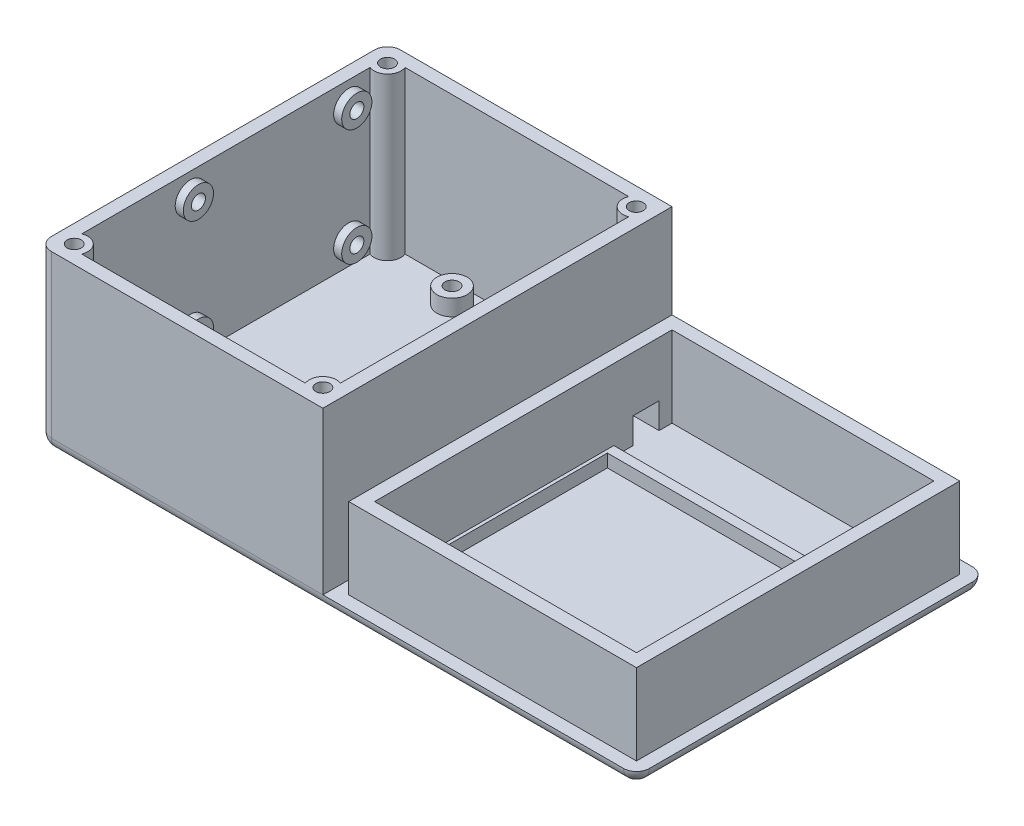
SolidWorks part; units mm, degrees
ref_plane "Front Plane" through (0, 0, 0) normal (0, 0, 1) x (1, 0, 0)
ref_plane "Top Plane" through (0, 0, 0) normal (0, 1, 0) x (1, 0, 0)
ref_plane "Right Plane" through (0, 0, 0) normal (1, 0, 0) x (0, 0, -1)
sketch "Sketch1" plane through (0, 0, 0) normal (0, 1, 0) x (1, 0, 0)
  line L1 (-88.5, -54) -> (88.5, -54)
  line L2 (-92.5, -50) -> (-92.5, 50)
  line L3 (-88.5, 54) -> (88.5, 54)
  line L4 (92.5, -50) -> (92.5, 50)
  line L5 (-92.5, -54) -> (92.5, 54) construction
  line L6 (-92.5, 54) -> (92.5, -54) construction
  arc A0 (-88.5, -54) -> (-92.5, -50) centre (-88.5, -50) cw
  arc A1 (88.5, -54) -> (92.5, -50) centre (88.5, -50) ccw
  arc A2 (88.5, 54) -> (92.5, 50) centre (88.5, 50) cw
  arc A3 (-92.5, 50) -> (-88.5, 54) centre (-88.5, 50) cw
  point P0 (0, 0)
  dimension "D1" = 4
  dimension "D2" = 185
  dimension "D3" = 100
extrude "Boss-Extrude1" add sketch "Sketch1" along normal blind 4
fillet "Fillet1" radius 4 8 edges at (0, 0, 54) (91.3284, 0, 52.8284) (92.5, 0, 0) (91.3284, 0, -52.8284) (0, 0, -54) (-91.3284, 0, -52.8284) (-92.5, 0, 0) (-91.3284, 0, 52.8284)
sketch "Sketch4" plane through (0, 4, 0) normal (0, 1, 0) x (1, 0, 0)
  line L0 (-88.5, -54) -> (88.5, -54) construction
  line L1 (92.5, -50) -> (92.5, 50) construction
  line L2 (88.5, 54) -> (-88.5, 54) construction
  line L3 (-92.5, 50) -> (-92.5, -50) construction
  line L4 (-88.5, -54) -> (88.5, -54)
  line L5 (92.5, -50) -> (92.5, 50)
  line L6 (88.5, 54) -> (-88.5, 54)
  line L7 (-92.5, 50) -> (-92.5, -50)
  line L8 (-88.5, -50) -> (88.5, -50)
  line L9 (88.5, -50) -> (88.5, 50)
  line L10 (88.5, 50) -> (-88.5, 50)
  line L11 (-88.5, 50) -> (-88.5, -50)
  line L12 (3.5, 46) -> (84.5, 46)
  line L13 (3.5, 54) -> (-0.5, 54)
  line L14 (3.5, 54) -> (3.5, -54)
  line L15 (3.5, -54) -> (-0.5, -54)
  line L16 (-0.5, 54) -> (-0.5, -54)
  line L17 (-4.5, 54) -> (-8.5, 54)
  line L18 (-4.5, 54) -> (-4.5, -54)
  line L19 (-4.5, -54) -> (-8.5, -54)
  line L20 (-8.5, 54) -> (-8.5, -54)
  line L21 (84.5, 46) -> (84.5, -46)
  line L22 (84.5, -46) -> (3.5, -46)
  arc A0 (-88.5, 54) -> (-92.5, 50) centre (-88.5, 50) ccw construction
  arc A1 (-92.5, -50) -> (-88.5, -54) centre (-88.5, -50) ccw construction
  arc A2 (88.5, -54) -> (92.5, -50) centre (88.5, -50) ccw construction
  arc A3 (92.5, 50) -> (88.5, 54) centre (88.5, 50) ccw construction
  arc A4 (-92.5, -50) -> (-88.5, -54) centre (-88.5, -50) ccw
  arc A5 (88.5, -54) -> (92.5, -50) centre (88.5, -50) ccw
  arc A6 (92.5, 50) -> (88.5, 54) centre (88.5, 50) ccw
  arc A7 (-88.5, 54) -> (-92.5, 50) centre (-88.5, 50) ccw
  arc A8 (88.5, -50) -> (88.5, -50) centre (88.5, -50) ccw
  arc A9 (88.5, 50) -> (88.5, 50) centre (88.5, 50) ccw
  arc A10 (-88.5, 50) -> (-88.5, 50) centre (-88.5, 50) ccw
  arc A11 (-88.5, -50) -> (-88.5, -50) centre (-88.5, -50) ccw
  arc M17 (-92.5, -50) -> (-88.5, -54) centre (-88.5, -50) ccw
  line M18 (-88.5, -54) -> (88.5, -54)
  line M22 (88.5, 54) -> (-88.5, 54)
  arc M23 (-88.5, 54) -> (-92.5, 50) centre (-88.5, 50) ccw
  line M24 (-92.5, 50) -> (-92.5, -50)
  dimension "D2" = 4
  dimension "D3" = 4
  dimension "D4" = 4
  dimension "D5" = 85
  dimension "D6" = 4
  dimension "D7" = 4
  dimension "D8" = 4
  dimension "D1" = 4
extrude "Boss-Extrude2" add sketch "Sketch4" along normal blind 50 contours L20 L8 L11 L10 M22 M23 M24 M17 M18 | L6 L20 L10 L18 | L10 L20 L8 L18 | L8 L20 L4 L18 region at (-90.361, 4, 51.861) region at (-6.5, 4, 52) region at (-6.5, 4, 0) region at (-6.5, 4, -52)
extrude "Boss-Extrude3" add sketch "Sketch4<3>" along normal blind 25 contours L10 L16 L8 L14 | L21 L22 L14 L8 L9 L10 L12 region at (1.5, 4, 0) region at (4.8124, 4, 48)
sketch "Sketch4<3>" plane through (0, 4, 0) normal (0, 1, 0) x (1, 0, 0) same geometry as "Sketch4"
sketch "Sketch5" plane through (-8.5, 0, 0) normal (-1, 0, 0) x (0, 0, 1)
  line L0 (-50, 4) -> (50, 4) construction
  line L1 (-42, 4) -> (-34, 4)
  line L2 (-42, 4) -> (-42, 12)
  line L3 (-42, 12) -> (-34, 12)
  line L4 (-34, 4) -> (-34, 12)
  line L6 (-46, 4) -> (-30, 4)
  line L7 (-46, 4) -> (-46, 16)
  line L8 (-46, 16) -> (-30, 16)
  line L9 (-30, 4) -> (-30, 16)
  line L10 (-50, 54) -> (-50, 4) construction
  point P6 (-38, 12)
  point P12 (-38, 16)
  line M5 (-50, 4) -> (50, 4)
  dimension "D1" = 8
  dimension "D2" = 4
  dimension "D3" = 4
  dimension "D4" = 4
extrude "Boss-Extrude4" add sketch "Sketch5" against normal up to surface (12 mm away) contours L9 L8 L7 L2 L3 L4 M5 region at (-8.5, 4.2, -44) up to face at (3.5, 16.5, 0)
extrude "Cut-Extrude1" cut sketch "Sketch5<3>" against normal up to surface (12 mm away) contours L4 L3 L2 M5 region at (-8.5, 8, -38) up to face at (3.5, 16.5, 0)
sketch "Sketch5<3>" plane through (-8.5, 0, 0) normal (-1, 0, 0) x (0, 0, 1) same geometry as "Sketch5"
sketch "Sketch6" plane through (0, 4, 0) normal (0, 1, 0) x (1, 0, 0)
  line L0 (5, 24.5) -> (83, 24.5) construction
  line L1 (4.5, 25) -> (83.5, 25)
  line L2 (4.5, 25) -> (4.5, -25)
  line L3 (4.5, -25) -> (83.5, -25)
  line L4 (83.5, 25) -> (83.5, -25)
  line L5 (5, -24.5) -> (5, 24.5) construction
  line L6 (88.5, -50) -> (88.5, 50) construction
  line L7 (88.5, 28) -> (3.5, 28)
  line L8 (88.5, 28) -> (88.5, -28)
  line L9 (88.5, -28) -> (3.5, -28)
  line L10 (3.5, 28) -> (3.5, -28)
  line L11 (3.5, 34) -> (3.5, -46) construction
  point P8 (5, 0)
  point P9 (4.5, 0)
  point P10 (44, 24.5)
  point P11 (44, 25)
  point P20 (3.5, 0)
  line M15 (3.5, 34) -> (3.5, -46)
  dimension "D1" = 0.5
  dimension "D2" = 0.5
  dimension "D3" = 3
extrude "Cut-Extrude2" cut sketch "Sketch6" against normal blind 1 contours L4 L1 L2 L3 region at (44, 4, 0)
extrude "Boss-Extrude5" add sketch "Sketch6<3>" along normal blind 3 contours L9 L7 L1 L4 L3 L2 M15 region at (87.4821, 4, 0)
sketch "Sketch6<3>" plane through (0, 4, 0) normal (0, 1, 0) x (1, 0, 0) same geometry as "Sketch6"
sketch "Sketch7" plane through (0, 4, 0) normal (0, 1, 0) x (1, 0, 0)
  line L2 (-88.5, 50) -> (-86.962, 48.462) construction
  line L3 (-8.5, 50) -> (-88.5, 50) construction
  line L4 (-4.5, 0) -> (-92.5, 0) construction
  line L5 (-4.5, 54) -> (-4.5, -54) construction
  line L6 (-92.5, 50) -> (-92.5, -50) construction
  line L7 (-48.5, -54) -> (-48.5, 54) construction
  line L8 (-88.5, -54) -> (-4.5, -54) construction
  line L9 (-4.5, 54) -> (-88.5, 54) construction
  line L10 (-8.5, 50) -> (-10.038, 48.462) construction
  line L11 (-8.5, -50) -> (-10.038, -48.462) construction
  line L12 (-88.5, -50) -> (-86.962, -48.462) construction
  circle A0 centre (-86.962, 48.462) radius 2.175
  circle A1 centre (-86.962, 48.462) radius 4.175
  circle A2 centre (-10.038, 48.462) radius 4.175
  circle A3 centre (-10.038, 48.462) radius 2.175
  circle A4 centre (-10.038, -48.462) radius 2.175
  circle A5 centre (-10.038, -48.462) radius 4.175
  circle A6 centre (-86.962, -48.462) radius 4.175
  circle A7 centre (-86.962, -48.462) radius 2.175
  point P21 (-48.5, 0)
  dimension "D1" = 4.35
  dimension "D2" = 2
  dimension "D3" = 45
extrude "Boss-Extrude6" add sketch "Sketch7" along normal up to surface (50 mm away) contours A1 | A2 | A6 | A5 up to face at (-48.5, 54, 0)
extrude "Cut-Extrude3" cut sketch "Sketch7<2>" against normal blind 5 from surface contours A0 | A3 | A4 | A7 starting at face at (-48.5, 54, 0)
sketch "Sketch7<2>" plane through (0, 4, 0) normal (0, 1, 0) x (1, 0, 0) same geometry as "Sketch7"
sketch "Sketch9" plane through (0, 4, 0) normal (0, 1, 0) x (1, 0, 0)
  line L0 (-13.9194, 50) -> (-83.0806, 50) construction
  line L2 (-8.5, 44.5806) -> (-8.5, -44.5806) construction
  circle A0 centre (-62.3, 43.75) radius 2.175
  circle A1 centre (-20.3, 43.75) radius 2.175
  circle A2 centre (-62.3, -16.25) radius 2.175
  circle A3 centre (-20.3, -16.25) radius 2.175
  circle A4 centre (-62.3, 43.75) radius 4.675
  circle A5 centre (-20.3, 43.75) radius 4.675
  circle A6 centre (-62.3, -16.25) radius 4.675
  circle A7 centre (-20.3, -16.25) radius 4.675
  dimension "D1" = 4.35
  dimension "D3" = 11.8
  dimension "D4" = 42
  dimension "D5" = 60
  dimension "D6" = 2.5
  dimension "D2" = 6.25
extrude "Boss-Extrude7" add sketch "Sketch9" along normal blind 5
sketch "Sketch10" plane through (-88.5, 0, 0) normal (1, 0, 0) x (0, 0, -1)
  circle A0 centre (-11, 47) radius 2.175
  circle A1 centre (38, 47) radius 2.175
  circle A2 centre (-11, 11) radius 2.175
  circle A3 centre (38, 11) radius 2.175
  circle A4 centre (-11, 47) radius 4.675
  circle A5 centre (38, 47) radius 4.675
  circle A6 centre (38, 11) radius 4.675
  circle A7 centre (-11, 11) radius 4.675
  dimension "D1" = 4.35
  dimension "D2" = 2.5
extrude "Boss-Extrude8" add sketch "Sketch10" along normal blind 2.5
extrude "Cut-Extrude4" cut sketch "Sketch10<2>" against normal offset from surface (2.5 mm away) 1.5 contours A1 | A3 | A2 | A0
sketch "Sketch10<2>" plane through (-88.5, 0, 0) normal (1, 0, 0) x (0, 0, -1) same geometry as "Sketch10"
equation "\"D3@Sketch4\"=\"D2@Sketch4\""
